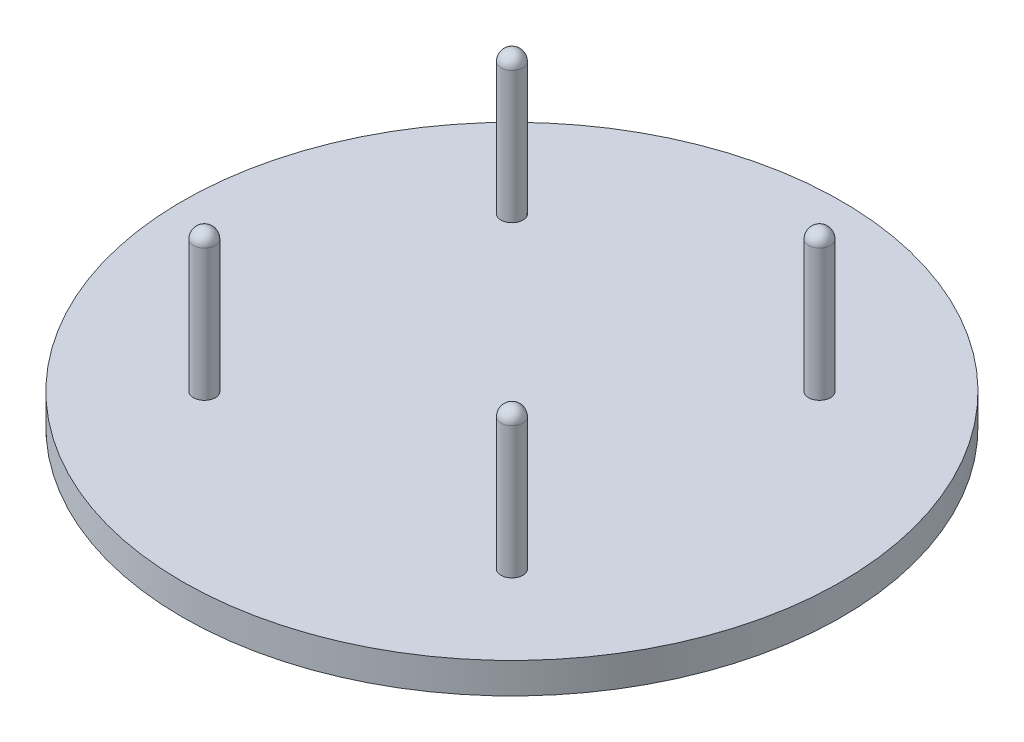
SolidWorks part; units mm, degrees
ref_plane "Front Plane" through (0, 0, 0) normal (0, 0, 1) x (1, 0, 0)
ref_plane "Top Plane" through (0, 0, 0) normal (0, 1, 0) x (1, 0, 0)
ref_plane "Right Plane" through (0, 0, 0) normal (1, 0, 0) x (0, 0, -1)
sketch "Sketch1" plane through (0, 0, 0) normal (0, 1, 0) x (1, 0, 0)
  circle A0 centre (0, 0) radius 75
  dimension "D1" = 150
extrude "Boss-Extrude1" add sketch "Sketch1" along normal blind 7
sketch "Sketch2" plane through (0, 7, 0) normal (0, 1, 0) x (1, 0, 0)
  line L0 (38.0095, 0) -> (0, 0) construction
  line L1 (0, 0) -> (35, 35) construction
  circle A0 centre (35, 35) radius 2.5
  dimension "D1" = 5
  dimension "D2" = 45
  dimension "D3" = 35
extrude "Boss-Extrude2" add sketch "Sketch2" along normal blind 30
dome "Dome1" faces to dome 1 distance 2.5 reverse direction no elliptical dome no face at (35, 37, -32.5) parameters "D1"=2.5
pattern_circular "CirPattern1" count 4 over 360 about axis through (0, 7, 0) along (0, -1, 0) of "Dome1", "Boss-Extrude2" reverse direction yes
